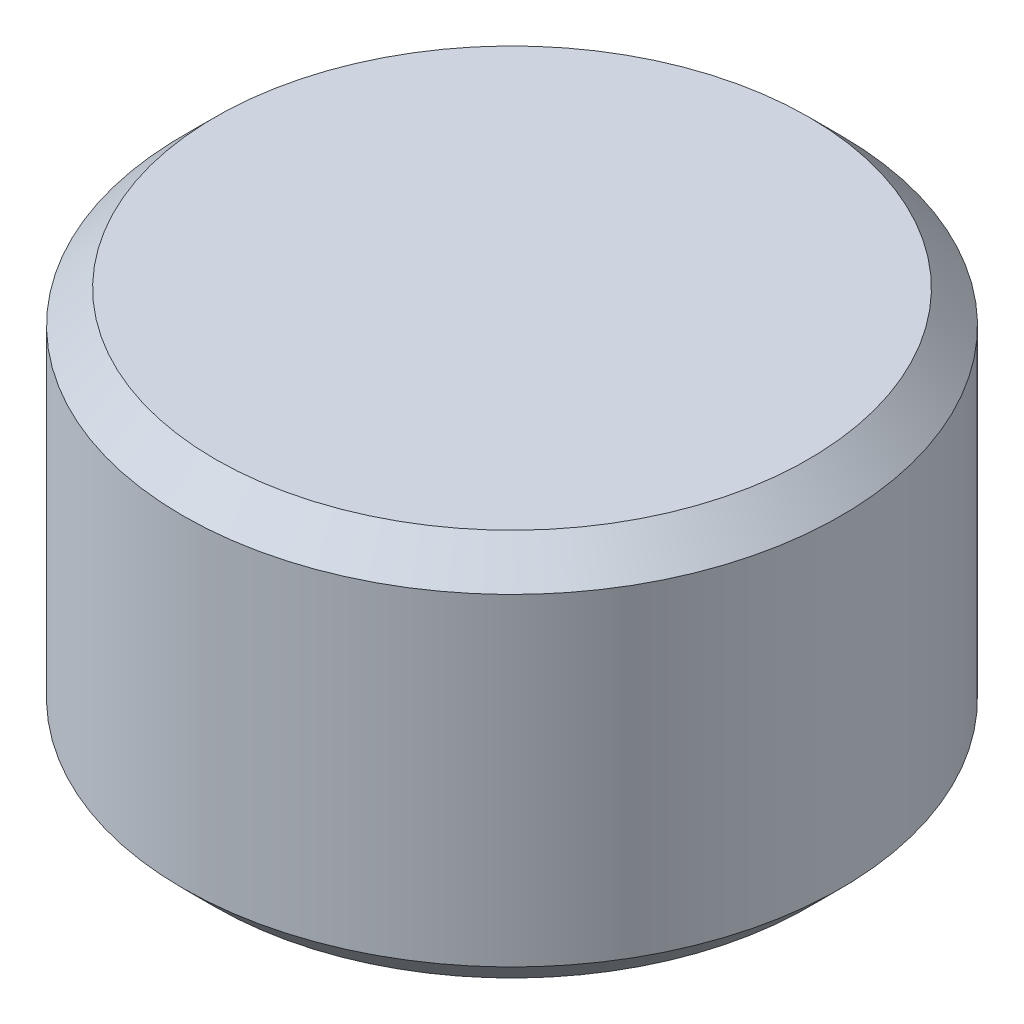
SolidWorks part; units mm, degrees
ref_plane "Front Plane" through (0, 0, 0) normal (0, 0, 1) x (1, 0, 0)
ref_plane "Top Plane" through (0, 0, 0) normal (0, 1, 0) x (1, 0, 0)
ref_plane "Right Plane" through (0, 0, 0) normal (1, 0, 0) x (0, 0, -1)
sketch "Sketch1" plane through (0, 0, 0) normal (0, 1, 0) x (1, 0, 0)
  circle A0 centre (0, 0) radius 10.1
  circle A1 centre (0, 0) radius 1.6
  dimension "D1" = 20.2
  dimension "D2" = 3.2
extrude "Boss-Extrude1" add sketch "Sketch1" along normal blind 11.9 contours A0
extrude "Cut-Extrude1" cut sketch "Sketch1<4>" along normal blind 6 contours A1 region at (0, 0, 0)
sketch "Sketch1<4>" plane through (0, 0, 0) normal (0, 1, 0) x (1, 0, 0) same geometry as "Sketch1"
chamfer "Chamfer1" distance 1 angle 45 2 edges at (0, 11.9, 10.1) (0, 0, 10.1)
